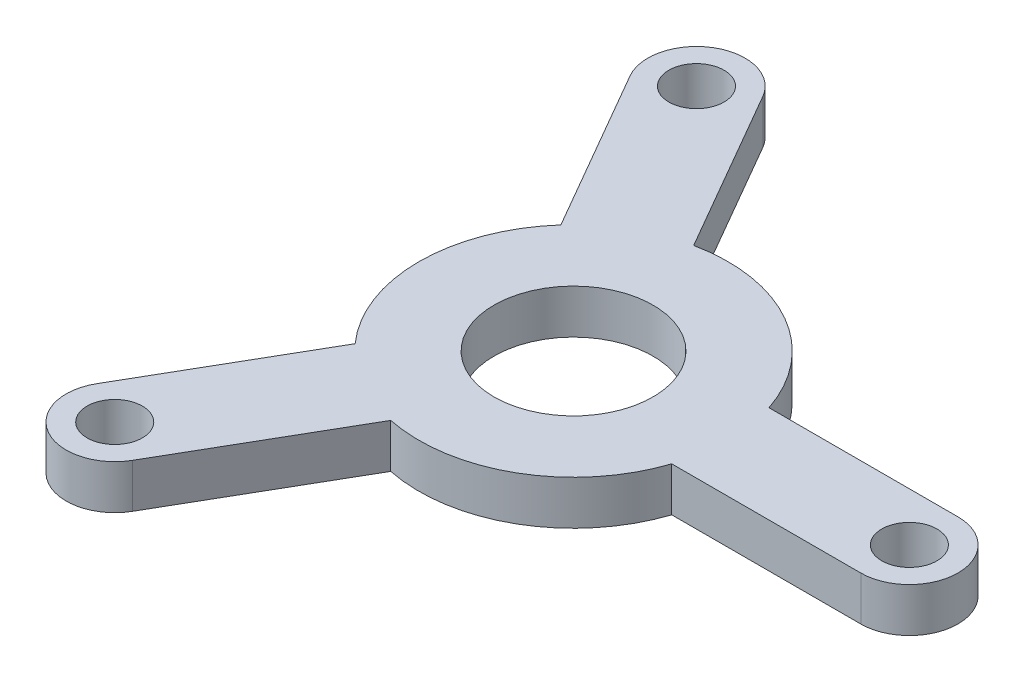
SolidWorks part; units mm, degrees
ref_plane "Front Plane" through (0, 0, 0) normal (0, 0, 1) x (1, 0, 0)
ref_plane "Top Plane" through (0, 0, 0) normal (0, 1, 0) x (1, 0, 0)
ref_plane "Right Plane" through (0, 0, 0) normal (1, 0, 0) x (0, 0, -1)
sketch "Sketch1" plane through (0, 0, 0) normal (0, 1, 0) x (1, 0, 0)
  circle A0 centre (0, 0) radius 9
  circle A1 centre (0, 0) radius 17.5
  dimension "D1" = 18
  dimension "D2" = 35
extrude "Boss-Extrude1" add sketch "Sketch1" along normal blind 5
sketch "Sketch3" plane through (0, 0, 0) normal (0, 1, 0) x (1, 0, 0)
  line L0 (0, 0) -> (38, 0) construction
  line L1 (10.0099, 5.5) -> (38, 5.5)
  line L2 (10.0099, 5.5) -> (10.0099, -5.5)
  line L3 (38, 5.5) -> (38, -5.5)
  line L4 (10.0099, -5.5) -> (38, -5.5)
  line L5 (38, 0) -> (10.0099, 0) construction
  line L6 (24.005, 5.5) -> (24.005, -5.5) construction
  circle A0 centre (0, 0) radius 38 construction
  circle A1 centre (38, 0) radius 5.5
  point P6 (24.005, 0)
  dimension "D1" = 76
  dimension "D2" = 11
  dimension "D3" = 11
extrude "Boss-Extrude3" add sketch "Sketch3" along normal up to surface (5 mm away) contours A1 L1 L2 L4 | L3 A1 | L3 A1 region at (21.8769, 0, 0) region at (40.3343, 0, 0) region at (35.6657, 0, 0) up to face at (0, 5, 17.5)
sketch "Sketch4" plane through (0, 5, 0) normal (0, 1, 0) x (1, 0, 0)
  circle A0 centre (38, 0) radius 3.125
  dimension "D1" = 6.25
extrude "Cut-Extrude1" cut sketch "Sketch4" against normal through all both and the other way through all
pattern_circular "CirPattern1" count 3 over 360 about axis through (0, 5, 0) along (0, 1, 0) of "Boss-Extrude3", "Cut-Extrude1"
